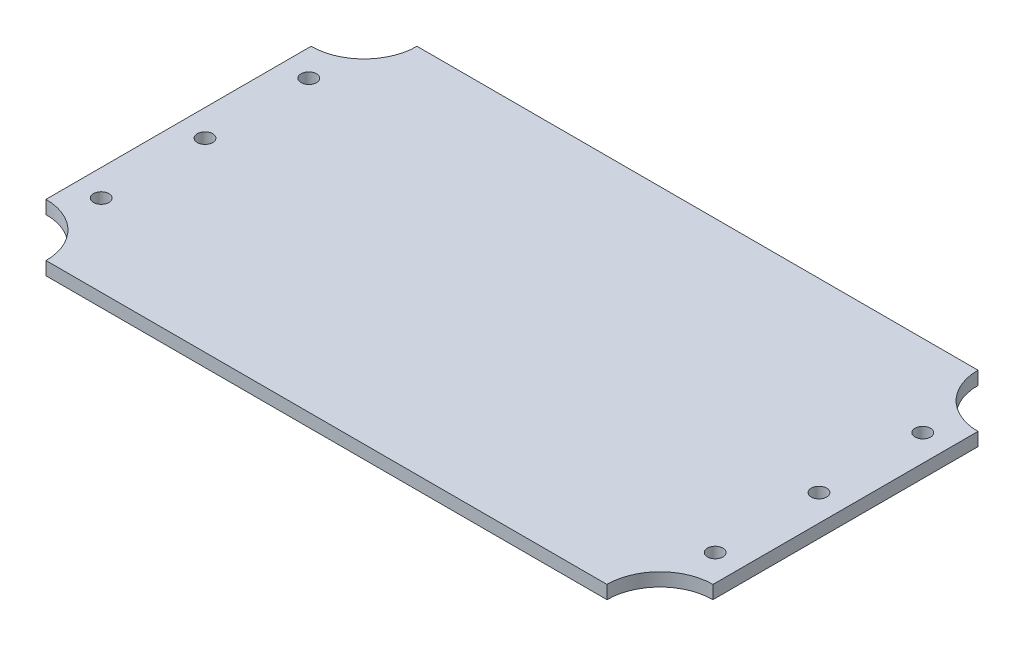
SolidWorks part; units mm, degrees
ref_plane "Спереди" through (0, 0, 0) normal (0, 0, 1) x (1, 0, 0)
ref_plane "Сверху" through (0, 0, 0) normal (0, 1, 0) x (1, 0, 0)
ref_plane "Справа" through (0, 0, 0) normal (1, 0, 0) x (0, 0, -1)
sketch "Эскиз2" plane through (0, 0, 0) normal (0, 0, 1) x (1, 0, 0)
  line L1 (-18.8586, 18.0445) -> (33.6414, 18.0445)
  line L2 (-18.8586, 18.0445) -> (-18.8586, 7.0445)
  line L3 (-9.8586, -13.9555) -> (16.6414, -13.9555)
  line L4 (34.6414, 17.0445) -> (34.6414, 7.0445)
  line L7 (33.6414, 6.0445) -> (22.6414, 6.0445)
  line L8 (17.6414, -12.9555) -> (17.6414, 1.0445)
  line L11 (-17.8586, 6.0445) -> (-10.8586, 6.0445)
  line L12 (-10.8586, -12.9555) -> (-10.8586, 6.0445)
  circle A0 centre (-0.8586, -3.9555) radius 4.5
  arc A1 (22.6414, 6.0445) -> (17.6414, 1.0445) centre (22.6414, 1.0445) ccw
  arc A2 (-17.8586, 6.0445) -> (-18.8586, 7.0445) centre (-17.8586, 7.0445) cw
  arc A3 (33.6414, 18.0445) -> (34.6414, 17.0445) centre (33.6414, 17.0445) cw
  arc A4 (33.6414, 6.0445) -> (34.6414, 7.0445) centre (33.6414, 7.0445) ccw
  arc A5 (-9.8586, -13.9555) -> (-10.8586, -12.9555) centre (-9.8586, -12.9555) cw
  arc A6 (16.6414, -13.9555) -> (17.6414, -12.9555) centre (16.6414, -12.9555) ccw
  point P12 (17.6414, 6.0445)
  point P15 (-18.8586, 6.0445)
  point P18 (34.6414, 18.0445)
  point P21 (34.6414, 6.0445)
  point P24 (-10.8586, -13.9555)
  point P27 (17.6414, -13.9555)
  dimension "D8" = 9
  dimension "D9" = 5
  dimension "D10" = 1
  dimension "D1" = 53.5
  dimension "D2" = 22
  dimension "D3" = 20
  dimension "D4" = 17
  dimension "D5" = 8
  dimension "D6" = 20
  dimension "D7" = 18
extrude "Бобышка-Вытянуть1" add sketch "Эскиз2" along normal blind 8
sketch "Эскиз3" plane through (0, 0, 8) normal (0, 0, 1) x (1, 0, 0)
  line L0 (-18.8586, 18.0445) -> (-18.8586, 7.0445) construction
  line L2 (33.6414, 18.0445) -> (-18.8586, 18.0445) construction
  line L3 (27.1414, 14.5445) -> (27.1414, 18.0445)
  line L4 (33.1414, 14.5445) -> (33.1414, 18.0445)
  line L5 (33.1414, 18.0445) -> (27.1414, 18.0445)
  line L6 (-0.3586, 14.5445) -> (-0.3586, 18.0445)
  line L7 (-6.3586, 14.5445) -> (-6.3586, 18.0445)
  line L8 (-6.3586, 18.0445) -> (-0.3586, 18.0445)
  line L9 (-6.3586, -10.4555) -> (-6.3586, -13.9555)
  line L10 (-9.8586, -13.9555) -> (16.6414, -13.9555) construction
  line L11 (-0.3586, -10.4555) -> (-0.3586, -13.9555)
  line L12 (-0.3586, -13.9555) -> (-6.3586, -13.9555)
  circle A0 centre (-3.3586, 14.5445) radius 1.5 construction
  circle A1 centre (30.1414, 14.5445) radius 1.5 construction
  circle A2 centre (-3.3586, -10.4555) radius 1.5 construction
  arc A3 (27.1414, 14.5445) -> (33.1414, 14.5445) centre (30.1414, 14.5445) ccw
  arc A4 (-6.3586, 14.5445) -> (-0.3586, 14.5445) centre (-3.3586, 14.5445) ccw
  arc A5 (-0.3586, -10.4555) -> (-0.9834, -8.6229) centre (-3.3586, -10.4555) ccw
  arc A6 (-3.5098, -7.5915) -> (-1.3272, -8.431) centre (-0.8586, -3.9555) ccw
  arc A7 (-3.8935, -7.5036) -> (-6.3586, -10.4555) centre (-3.3586, -10.4555) ccw
  arc A8 (-0.9834, -8.6229) -> (-1.3272, -8.431) centre (-1.3792, -8.9283) ccw
  arc A9 (-3.5098, -7.5915) -> (-3.8935, -7.5036) centre (-3.8044, -7.9955) ccw
  point P32 (-3.6672, -7.4714)
  dimension "D3" = 3
  dimension "D4" = 33.5
  dimension "D6" = 6
  dimension "D7" = 9
  dimension "D8" = 0.5
  dimension "D1" = 15.5
  dimension "D2" = 3.5
  dimension "D5" = 25
extrude "Бобышка-Вытянуть2" add sketch "Эскиз3" along normal blind 4 and the other way blind 11.5
sketch "Эскиз5" plane through (0, 0, 8) normal (0, 0, 1) x (1, 0, 0)
  line L1 (8.5209, 6.5605) -> (2.5209, 6.5605)
  line L2 (11.5209, 3.5605) -> (11.5209, -5.4395)
  line L3 (8.5209, -8.4395) -> (-0.4791, -8.4395)
  line L4 (-0.4791, 3.5605) -> (-0.4791, -8.4395)
  arc A0 (-1.3272, -8.431) -> (-3.5098, -7.5915) centre (-0.8586, -3.9555) ccw construction
  arc A1 (8.5209, -8.4395) -> (11.5209, -5.4395) centre (8.5209, -5.4395) ccw
  arc A2 (11.5209, 3.5605) -> (8.5209, 6.5605) centre (8.5209, 3.5605) ccw
  arc A3 (-0.4791, 3.5605) -> (2.5209, 6.5605) centre (2.5209, 3.5605) cw
  point P9 (11.5209, -8.4395)
  point P12 (11.5209, 6.5605)
  dimension "D3" = 3
  dimension "D1" = 15
  dimension "D2" = 12
extrude "Вырез-Вытянуть1" cut sketch "Эскиз5" against normal through all both and the other way through all
sketch "Эскиз6" plane through (0, 0, 8) normal (0, 0, 1) x (1, 0, 0)
  circle A0 centre (-3.3586, 14.5445) radius 1
  circle A1 centre (30.1414, 14.5445) radius 1
  circle A2 centre (-3.3586, -10.4555) radius 1
  dimension "D1" = 2
extrude "Вырез-Вытянуть2" cut sketch "Эскиз6" against normal through all both and the other way through all
sketch "Эскиз7" plane through (0, 18.0445, 0) normal (0, 1, 0) x (1, 0, 0)
  line L1 (-31.8586, 15.5) -> (95.1414, 15.5)
  line L2 (-43.8586, 3.5) -> (-43.8586, -56.5)
  line L3 (-31.8586, -68.5) -> (95.1414, -68.5)
  line L4 (107.1414, 3.5) -> (107.1414, -56.5)
  line L5 (-43.8586, -26.5) -> (107.1414, -26.5) construction
  line L6 (-0.3586, 3.5) -> (-6.3586, 3.5) construction
  line L7 (31.6414, 15.5) -> (31.6414, -68.5) construction
  arc A0 (-43.8586, 3.5) -> (-31.8586, 15.5) centre (-43.8586, 15.5) ccw
  arc A1 (95.1414, 15.5) -> (107.1414, 3.5) centre (107.1414, 15.5) ccw
  arc A2 (107.1414, -56.5) -> (95.1414, -68.5) centre (107.1414, -68.5) ccw
  arc A3 (-31.8586, -68.5) -> (-43.8586, -56.5) centre (-43.8586, -68.5) ccw
  circle A4 centre (-37.8586, -26.5) radius 1.75
  circle A5 centre (-37.8586, -50) radius 1.75
  circle A6 centre (-37.8586, -3) radius 1.75
  circle A7 centre (101.1414, -50) radius 1.75
  circle A8 centre (101.1414, -26.5) radius 1.75
  circle A9 centre (101.1414, -3) radius 1.75
  dimension "D3" = 24
  dimension "D7" = 3.5
  dimension "D1" = 151
  dimension "D2" = 84
  dimension "D4" = 12
  dimension "D5" = 25
  dimension "D8" = 23.5
  dimension "D6" = 23.5
  dimension "D9" = 6
extrude "Бобышка-Вытянуть3" add sketch "Эскиз7" along normal blind 3
sketch "Эскиз8" plane through (0, 18.0445, 0) normal (0, -1, 0) x (1, 0, 0)
  line L0 (107.1414, 56.5) -> (107.1414, -3.5) construction
  line L1 (90.1414, 31) -> (44.1414, 31)
  line L2 (92.1414, 29) -> (92.1414, 28)
  line L3 (90.1414, 26) -> (44.1414, 26)
  line L4 (42.1414, 29) -> (42.1414, 28)
  line L5 (33.1414, 12) -> (27.1414, 12) construction
  line L6 (42.1414, 28.5) -> (92.1414, 28.5) construction
  arc A0 (92.1414, 28) -> (90.1414, 26) centre (90.1414, 28) cw
  arc A1 (92.1414, 29) -> (90.1414, 31) centre (90.1414, 29) ccw
  arc A2 (44.1414, 26) -> (42.1414, 28) centre (44.1414, 28) cw
  arc A3 (42.1414, 29) -> (44.1414, 31) centre (44.1414, 29) cw
  point P10 (92.1414, 26)
  point P13 (92.1414, 31)
  point P16 (42.1414, 26)
  dimension "D5" = 2
  dimension "D1" = 5
  dimension "D2" = 50
  dimension "D3" = 15
  dimension "D4" = 14
extrude "Бобышка-Вытянуть4" add sketch "Эскиз8" along normal blind 5
sketch "Эскиз9" plane through (0, 13.0445, 0) normal (0, -1, 0) x (1, 0, 0)
  line L0 (42.1414, 28.5) -> (92.1414, 28.5) construction
  line L1 (42.1414, 29) -> (42.1414, 28) construction
  line L2 (92.1414, 28) -> (92.1414, 29) construction
  line L3 (67.1414, 31) -> (67.1414, 26) construction
  line L4 (90.1414, 31) -> (44.1414, 31) construction
  line L5 (44.1414, 26) -> (90.1414, 26) construction
  circle A0 centre (67.1414, 28.5) radius 1
  circle A1 centre (72.1414, 28.5) radius 1
  circle A2 centre (77.1414, 28.5) radius 1
  circle A3 centre (82.1414, 28.5) radius 1
  circle A4 centre (87.1414, 28.5) radius 1
  circle A5 centre (47.1414, 28.5) radius 1
  circle A6 centre (52.1414, 28.5) radius 1
  circle A7 centre (57.1414, 28.5) radius 1
  circle A8 centre (62.1414, 28.5) radius 1
  dimension "D1" = 2
  dimension "D2" = 5
extrude "Вырез-Вытянуть3" cut sketch "Эскиз9" against normal blind 5
sketch "Эскиз10" plane through (0, 18.0445, 0) normal (0, -1, 0) x (1, 0, 0)
  line L0 (-43.8586, -3.5) -> (-43.8586, 56.5) construction
  line L1 (26.1414, 57.5) -> (70.1414, 57.5) construction
  line L2 (26.1414, 57.5) -> (26.1414, 36.5) construction
  line L3 (26.1414, 36.5) -> (70.1414, 36.5) construction
  line L4 (70.1414, 57.5) -> (70.1414, 36.5) construction
  line L5 (95.1414, -15.5) -> (-31.8586, -15.5) construction
  line L6 (-6.8586, 57.5) -> (-6.8586, 29.5) construction
  line L7 (-31.8586, 57.5) -> (18.1414, 57.5) construction
  line L8 (-31.8586, 57.5) -> (-31.8586, 29.5) construction
  line L9 (-31.8586, 29.5) -> (18.1414, 29.5) construction
  line L10 (18.1414, 57.5) -> (18.1414, 29.5) construction
  line L11 (-31.8586, 43.5) -> (18.1414, 43.5) construction
  circle A0 centre (32.6414, 55) radius 3.5
  circle A1 centre (63.6414, 39) radius 3.5
  circle A2 centre (32.6414, 55) radius 1
  circle A3 centre (63.6414, 39) radius 1
  circle A4 centre (-28.2586, 54) radius 3.5
  circle A5 centre (-28.2586, 54) radius 1
  circle A6 centre (14.5414, 54) radius 1
  circle A7 centre (14.5414, 54) radius 3.5
  circle A8 centre (14.5414, 33) radius 1
  circle A9 centre (14.5414, 33) radius 3.5
  circle A10 centre (-28.2586, 33) radius 1
  circle A11 centre (-28.2586, 33) radius 3.5
  point P20 (-6.8586, 57.5)
  point P21 (-31.8586, 43.5)
  dimension "D3" = 7
  dimension "D6" = 6.5
  dimension "D10" = 2
  dimension "D1" = 44
  dimension "D2" = 21
  dimension "D4" = 6.5
  dimension "D5" = 2.5
  dimension "D7" = 2.5
  dimension "D8" = 70
  dimension "D9" = 52
  dimension "D11" = 50
  dimension "D12" = 28
  dimension "D13" = 12
  dimension "D14" = 45
  dimension "D15" = 21.4
  dimension "D16" = 10.5
extrude "Бобышка-Вытянуть5" add sketch "Эскиз10" along normal blind 4
equation "\"D6@Эскиз7\"=\"D8@Эскиз7\""
